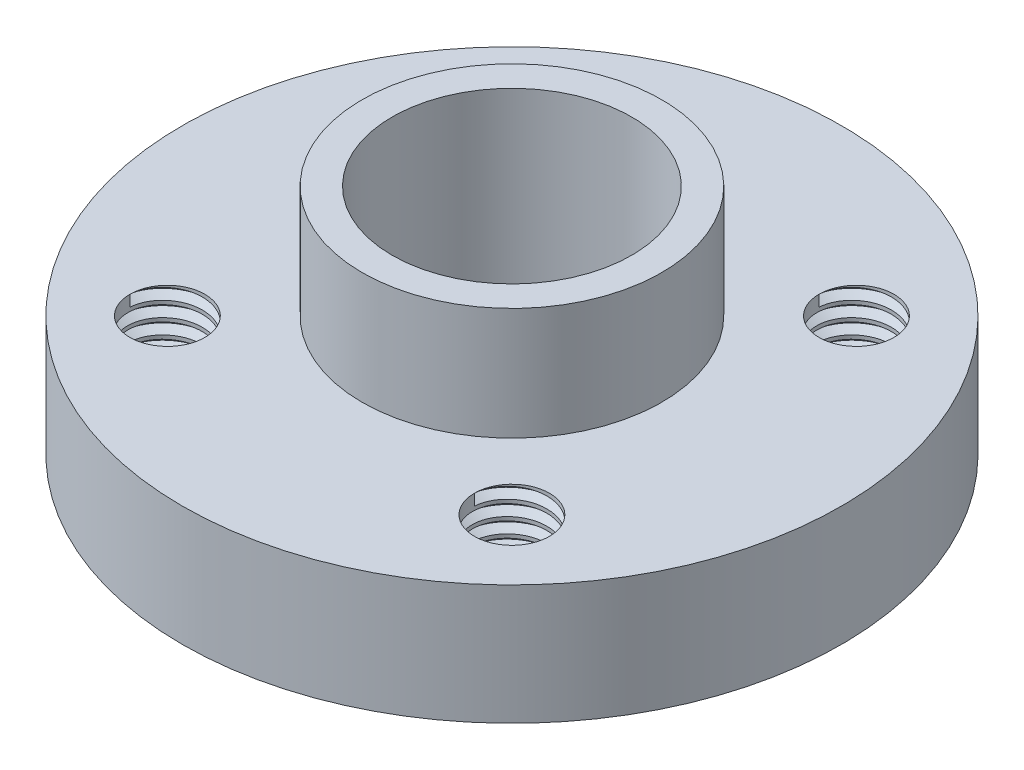
SolidWorks part; units mm, degrees
ref_plane "Front Plane" through (0, 0, 0) normal (0, 0, 1) x (1, 0, 0)
ref_plane "Top Plane" through (0, 0, 0) normal (0, 1, 0) x (1, 0, 0)
ref_plane "Right Plane" through (0, 0, 0) normal (1, 0, 0) x (0, 0, -1)
sketch "Sketch1" plane through (0, 0, 0) normal (0, 1, 0) x (1, 0, 0)
  circle A0 centre (0, 0) radius 11
  dimension "D1" = 22
extrude "Boss-Extrude1" add sketch "Sketch1" along normal blind 4
sketch "Sketch2" plane through (0, 4, 0) normal (0, 1, 0) x (1, 0, 0)
  circle A0 centre (0, 0) radius 5
  dimension "D1" = 10
extrude "Boss-Extrude2" add sketch "Sketch2" along normal blind 3.75
sketch "Sketch3" plane through (0, 0, 0) normal (0, -1, 0) x (1, 0, 0)
  circle A0 centre (0, 0) radius 5
  dimension "D1" = 10
extrude "Boss-Extrude3" add sketch "Sketch3" along normal blind 3.75
sketch "Sketch4" plane through (0, 4, 0) normal (0, 1, 0) x (1, 0, 0)
  line L0 (0, 0) -> (0, 11) construction
  circle A0 centre (-5.75, 5.75) radius 1.5
  circle A1 centre (0, 0) radius 11 construction
  circle A2 centre (5.75, 5.75) radius 1.5
  circle A3 centre (5.75, -5.75) radius 1.5
  circle A4 centre (-5.75, -5.75) radius 1.5
  point P17 (0, 0)
  dimension "D3" = 3
  dimension "D1" = 5.75
  dimension "D2" = 5.75
  dimension "D4" = 4
hole_wizard "Ø8.0 (8) Diameter Hole2" positions "Sketch9" profile "Sketch10" hole size "Ø8.0" standard "ANSI Metric" end condition through all
sketch "Sketch9" plane through (0, 7.75, 0) normal (0, 1, 0) x (1, 0, 0)
  point P0 (0, 0)
sketch "Sketch10" plane through (0, 7.75, 0) normal (1, 0, 0) x (0, 0, 1)
  line L0 (0, 0) -> (0, 11.5)
  line L1 (0, 11.5) -> (4, 11.5)
  line L2 (4, 11.5) -> (4, 0)
  line L5 (4, 0) -> (0, 0)
  line L11 (0, -6.35) -> (0, 107.95) construction
  dimension "Thru Hole Dia." = 8
  dimension "Thru Hole Depth" = 11.5
hole_wizard "Tap Drill for M3x0.5 Tap1" positions "Sketch11" profile "Sketch12" hole size "M3x0.5" standard "ANSI Metric" end condition through all
sketch "Sketch11" plane through (0, 4, 0) normal (0, 1, 0) x (1, 0, 0)
  point P0 (-5.75, -5.75)
  point P3 (-5.75, 5.75)
  point P6 (5.75, 5.75)
  point P9 (5.75, -5.75)
sketch "Sketch12" plane through (-5.75, 4, 5.75) normal (1, 0, 0) x (0, 0, 1)
  line L0 (0, 0) -> (0, 7.75)
  line L1 (0, 7.75) -> (1.25, 7.75)
  line L2 (1.25, 7.75) -> (1.25, 0)
  line L5 (1.25, 0) -> (0, 0)
  line L11 (0, -6.35) -> (0, 107.95) construction
  dimension "Thru Hole Dia." = 2.5
  dimension "Thru Hole Depth" = 7.75
thread "Thread1" pitch 0.5 method cut profile "Thread Profile1" start angle 0, offset 0, length 0, pitch 0.5, diameter 2.5
ref_plane "Plane1" through (-7, 4, -5.75) normal (0, 0, 1) x (-1, 0, 0)
sketch "Thread Profile1" plane through (-7, 4, -5.75) normal (0, 0, 1) x (-1, 0, 0)
  line L0 (0, 0) -> (0, 0.5) construction
  line L1 (0, 0) -> (0.2706, 0.1562)
  line L2 (0.2706, 0.1562) -> (0.2706, 0.2187)
  line L3 (0.2706, 0.2187) -> (0, 0.375)
  line L4 (0.2706, 0.1875) -> (0, 0.1875) construction
  line L11 (0, 0) -> (0, 0.375)
  point P2 (0, 0)
  dimension "Pitch" = 0.5
  dimension "Profile_Angle" = 60
  dimension "Profile_Land" = 0.0625
  dimension "Profile_Height" = 0.2706
thread "Thread2" pitch 0.5 method cut profile "Thread Profile2" start angle 0, offset 0, length 0, pitch 0.5, diameter 2.5
ref_plane "Plane2" through (-7, 4, 5.75) normal (0, 0, 1) x (-1, 0, 0)
sketch "Thread Profile2" plane through (-7, 4, 5.75) normal (0, 0, 1) x (-1, 0, 0)
  line L0 (0, 0) -> (0, 0.5) construction
  line L1 (0, 0) -> (0.2706, 0.1562)
  line L2 (0.2706, 0.1562) -> (0.2706, 0.2187)
  line L3 (0.2706, 0.2187) -> (0, 0.375)
  line L4 (0.2706, 0.1875) -> (0, 0.1875) construction
  line L11 (0, 0) -> (0, 0.375)
  point P2 (0, 0)
  dimension "Pitch" = 0.5
  dimension "Profile_Angle" = 60
  dimension "Profile_Land" = 0.0625
  dimension "Profile_Height" = 0.2706
thread "Thread3" pitch 0.5 method cut profile "Thread Profile3" start angle 0, offset 0, length 0, pitch 0.5, diameter 2.5
ref_plane "Plane3" through (4.5, 4, 5.75) normal (0, 0, 1) x (-1, 0, 0)
sketch "Thread Profile3" plane through (4.5, 4, 5.75) normal (0, 0, 1) x (-1, 0, 0)
  line L0 (0, 0) -> (0, 0.5) construction
  line L1 (0, 0) -> (0.2706, 0.1562)
  line L2 (0.2706, 0.1562) -> (0.2706, 0.2187)
  line L3 (0.2706, 0.2187) -> (0, 0.375)
  line L4 (0.2706, 0.1875) -> (0, 0.1875) construction
  line L11 (0, 0) -> (0, 0.375)
  point P2 (0, 0)
  dimension "Pitch" = 0.5
  dimension "Profile_Angle" = 60
  dimension "Profile_Land" = 0.0625
  dimension "Profile_Height" = 0.2706
thread "Thread4" pitch 0.5 method cut profile "Thread Profile4" start angle 0, offset 0, length 0, pitch 0.5, diameter 2.5
ref_plane "Plane4" through (4.5, 4, -5.75) normal (0, 0, 1) x (-1, 0, 0)
sketch "Thread Profile4" plane through (4.5, 4, -5.75) normal (0, 0, 1) x (-1, 0, 0)
  line L0 (0, 0) -> (0, 0.5) construction
  line L1 (0, 0) -> (0.2706, 0.1562)
  line L2 (0.2706, 0.1562) -> (0.2706, 0.2187)
  line L3 (0.2706, 0.2187) -> (0, 0.375)
  line L4 (0.2706, 0.1875) -> (0, 0.1875) construction
  line L11 (0, 0) -> (0, 0.375)
  point P2 (0, 0)
  dimension "Pitch" = 0.5
  dimension "Profile_Angle" = 60
  dimension "Profile_Land" = 0.0625
  dimension "Profile_Height" = 0.2706
